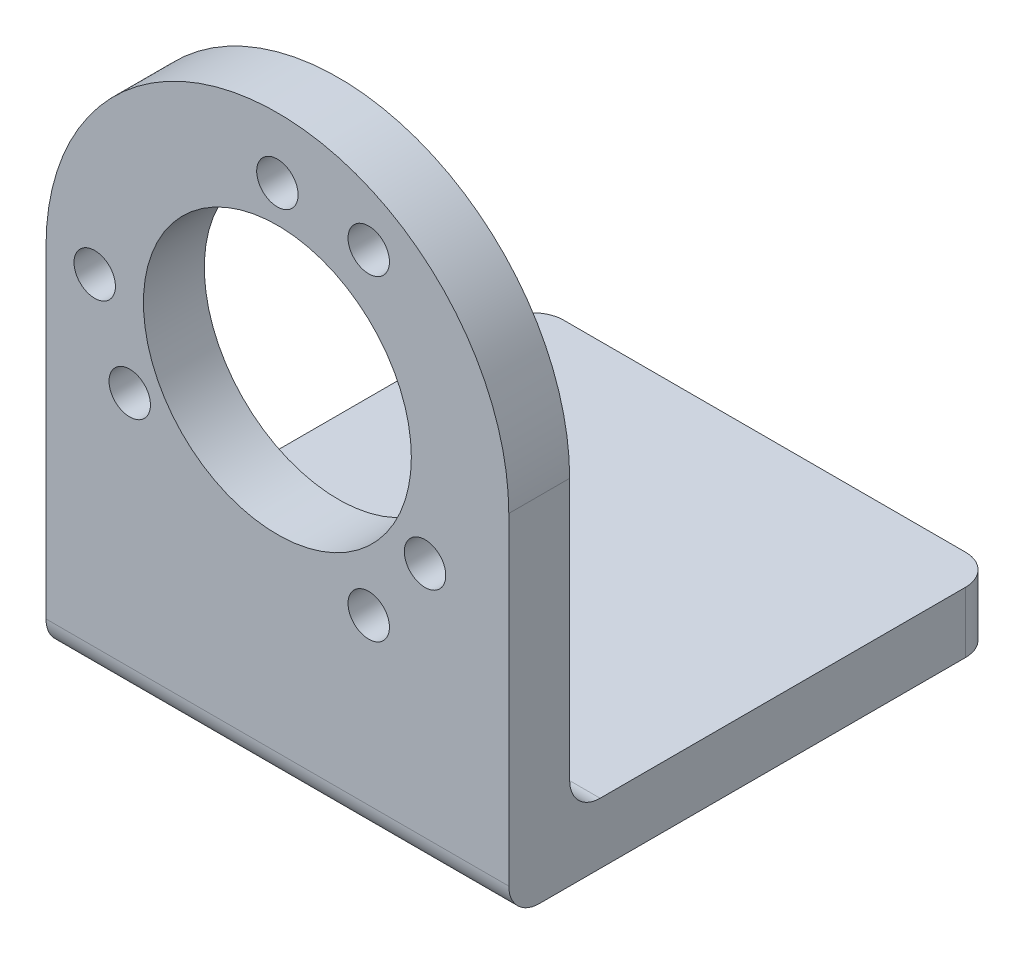
SolidWorks part; units mm, degrees
material "ABS"
ref_plane "Front Plane" through (0, 0, 0) normal (0, 0, 1) x (1, 0, 0)
ref_plane "Top Plane" through (0, 0, 0) normal (0, 1, 0) x (1, 0, 0)
ref_plane "Right Plane" through (0, 0, 0) normal (1, 0, 0) x (0, 0, -1)
sketch "Sketch1" plane through (0, 0, 0) normal (0, 0, 1) x (1, 0, 0)
  line L0 (-19, 0) -> (-19, -29)
  line L1 (-19, -29) -> (19, -29)
  line L2 (19, -29) -> (19, 0)
  circle A0 centre (0, 0) radius 19
  circle A1 centre (0, 0) radius 11
  dimension "D1" = 38
  dimension "D2" = 10
  dimension "D3" = 22
extrude "Boss-Extrude1" add sketch "Sketch1" along normal blind 5 contours A0 A1 | A0 L0 L1 L2 region at (0, -21.3225, 0) region at (0, 18.4626, 0)
sketch "Sketch2" plane through (0, 0, 0) normal (0, 0, -1) x (-1, 0, 0)
  line L0 (19, 0) -> (19, -29) construction
  line L1 (-19, -29) -> (19, -29)
  line L2 (-19, -29) -> (-19, -24)
  line L3 (-19, -24) -> (19, -24)
  line L4 (19, -29) -> (19, -24)
  dimension "D1" = 5
extrude "Boss-Extrude2" add sketch "Sketch2" along normal blind 35
hole_wizard "M3 Clearance Hole1" positions "Sketch3" profile "Sketch4" hole size "M3" standard "ANSI Metric" end condition up to next
sketch "Sketch3" plane through (0, 0, 5) normal (0, 0, 1) x (1, 0, 0)
  line L0 (0, 0) -> (0, 14) construction
  line L2 (0, 0) -> (7.5, 12.9904) construction
  circle A0 centre (0, 0) radius 14 construction
  circle A1 centre (0, 0) radius 15 construction
  point P5 (0, 14)
  point P14 (12.1244, -7)
  point P15 (-12.1244, -7)
  point P19 (7.5, 12.9904)
  point P32 (7.5, -12.9904)
  point P33 (-15, 0)
  dimension "D1" = 28
  dimension "D2" = 3
  dimension "D3" = 30
  dimension "D4" = 30
sketch "Sketch4" plane through (-15, 0, 5) normal (1, 0, 0) x (0, -1, 0)
  line L0 (0, 0) -> (0, 5)
  line L1 (0, 5) -> (1.7, 5)
  line L2 (1.7, 5) -> (1.7, 0)
  line L5 (1.7, 0) -> (0, 0)
  line L11 (0, -6.35) -> (0, 107.95) construction
  dimension "Thru Hole Dia." = 3.4
  dimension "Thru Hole Depth" = 5
fillet "Fillet1" radius 2.5 4 edges at (-19, -26.5, -35) (19, -26.5, -35) (0, -24, 0) (0, -29, 5)
